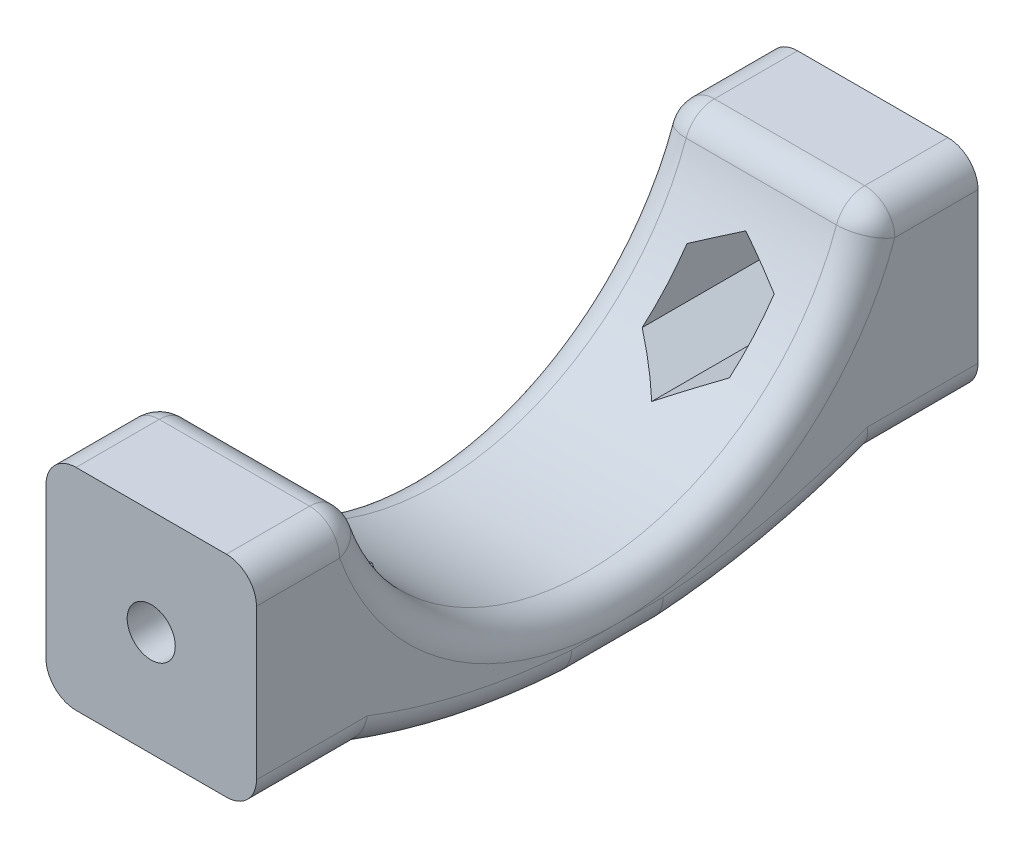
SolidWorks part; units mm, degrees
ref_plane "Front Plane" through (0, 0, 0) normal (0, 0, 1) x (1, 0, 0)
ref_plane "Top Plane" through (0, 0, 0) normal (0, 1, 0) x (1, 0, 0)
ref_plane "Right Plane" through (0, 0, 0) normal (1, 0, 0) x (0, 0, -1)
sketch "Sketch1" plane through (0, 0, 0) normal (0, 0, 1) x (1, 0, 0)
  line L1 (0, 0) -> (14, 0)
  line L2 (0, 0) -> (0, 17)
  line L3 (0, 17) -> (14, 17)
  line L4 (14, 0) -> (14, 17)
  circle A0 centre (7, 10) radius 1.6
extrude "Boss-Extrude1" add sketch "Sketch1" along normal blind 48
sketch "Sketch2" plane through (0, 0, 0) normal (-1, 0, 0) x (0, 0, 1)
  line L0 (48, 0) -> (48, 3)
  line L1 (48, 17) -> (48, 0) construction
  line L2 (0, 0) -> (0, 3)
  line L3 (0, 17) -> (0, 0) construction
  line L4 (48, 3) -> (41, 3)
  line L5 (0, 3) -> (7, 3)
  line L7 (48, 0) -> (27.102, 0)
  line L8 (48, 17) -> (0, 17) construction
  line L9 (20.898, 0) -> (0, 0)
  line L10 (41, 17) -> (7, 17)
  arc A1 (7, 17) -> (41, 17) centre (24, 21.6154) ccw
  arc A2 (7, 3) -> (20.898, 0) centre (24, 48.0629) ccw
  arc A3 (27.102, 0) -> (41, 3) centre (24, 48.0629) ccw
extrude "Cut-Extrude1" cut sketch "Sketch2" against normal up to surface (14 mm away) up to face at (14, 8.5, 24)
sketch "Sketch3" plane through (0, 0, 48) normal (0, 0, 1) x (1, 0, 0)
  line L1 (7, 6.6514) -> (9.9, 8.3257)
  line L2 (9.9, 8.3257) -> (9.9, 11.6743)
  line L3 (9.9, 11.6743) -> (7, 13.3486)
  line L4 (7, 13.3486) -> (4.1, 11.6743)
  line L5 (4.1, 11.6743) -> (4.1, 8.3257)
  line L6 (4.1, 8.3257) -> (7, 6.6514)
  circle A0 centre (7, 10) radius 2.9 construction
extrude "Cut-Extrude2" cut sketch "Sketch3" against normal offset from surface (40 mm away) 4 from offset 4 up to face at (7, 10, 0) offset against normal yes
fillet "Fillet1" radius 2 18 edges at (0, 3, 44.5) (0, 0.9843, 34.1623) (0, 0, 24) (0, 0.9843, 13.8377) (0, 3, 3.5) (14, 3, 44.5) (14, 0.9843, 13.8377) (14, 0, 24) (14, 3, 3.5) (14, 0.9843, 34.1623) (14, 17, 44.5) (7, 17, 41) (0, 17, 44.5) (7, 17, 7) (0, 4, 24) (14, 4, 24) (0, 17, 3.5) (14, 17, 3.5)
